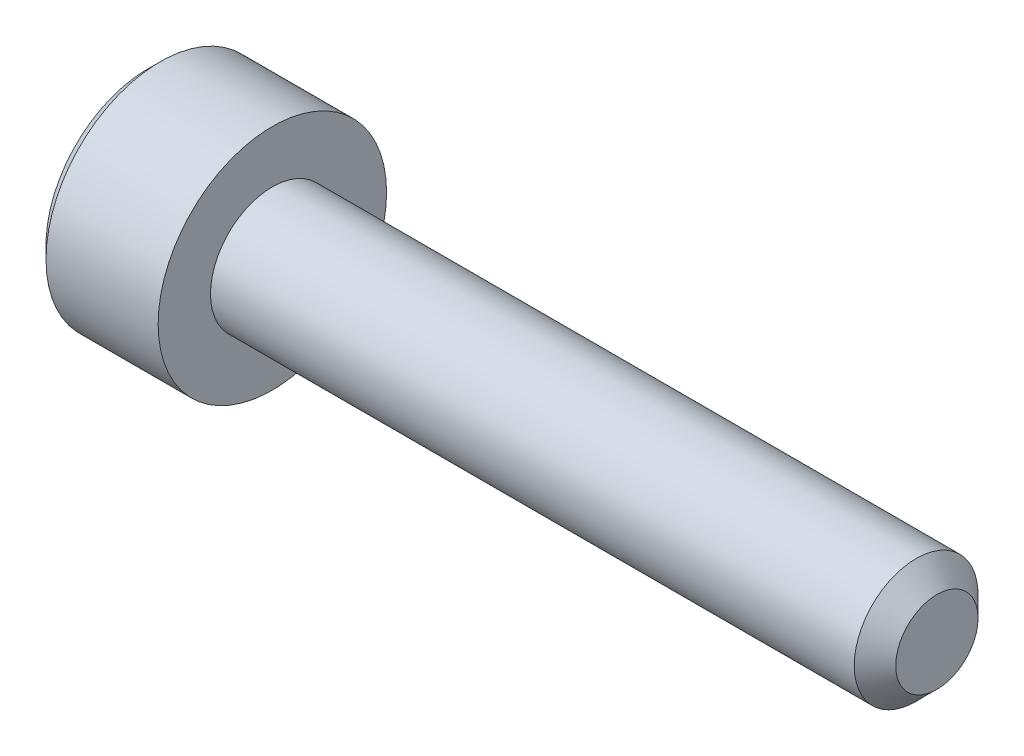
SolidWorks part; units mm, degrees
material "AISI Type 316L stainless steel"
ref_plane "Front Plane" through (0, 0, 0) normal (0, 0, 1) x (1, 0, 0)
ref_plane "Top Plane" through (0, 0, 0) normal (0, 1, 0) x (1, 0, 0)
ref_plane "Right Plane" through (0, 0, 0) normal (1, 0, 0) x (0, 0, -1)
sketch "Sketch1" plane through (0, 0, 0) normal (0, 0, 1) x (1, 0, 0)
  line L0 (-88.7055, 0) -> (96.9812, 0) construction
  line L1 (0, 0) -> (0, 2.75)
  line L2 (0, 2.75) -> (3, 2.75)
  line L4 (19, 0) -> (19, 1.49)
  line L5 (19, 1.49) -> (3, 1.49)
  line L6 (3, 1.49) -> (3, 2.75)
  line L7 (0, 0) -> (19, 0)
  dimension "D1" = 16
  dimension "D2" = 3
  dimension "D3" = 2.75
  dimension "D4" = 1.49
revolve "Revolve1" add sketch "Sketch1" angle 360 about L0
chamfer "Chamfer1" distance 0.5 angle 45 1 edges at (19, 0, 1.49)
chamfer "Chamfer2" distance 0.3 angle 45 1 edges at (0, 0, 2.75)
sketch "Sketch3" plane through (0, 0, 0) normal (1, 0, 0) x (0, 0, -1)
  line L1 (-1.4434, 0) -> (-0.7217, -1.25)
  line L2 (-0.7217, -1.25) -> (0.7217, -1.25)
  line L3 (0.7217, -1.25) -> (1.4434, 0)
  line L4 (1.4434, 0) -> (0.7217, 1.25)
  line L5 (0.7217, 1.25) -> (-0.7217, 1.25)
  line L6 (-0.7217, 1.25) -> (-1.4434, 0)
  circle A0 centre (0, 0) radius 1.25 construction
extrude "Cut-Extrude1" cut sketch "Sketch3" along normal blind 2.5
chamfer "Chamfer3" distance 0.3 angle 45 6 edges at (0, 1.25, 0) (0, 0.625, 1.0825) (0, -0.625, 1.0825) (0, -1.25, 0) (0, -0.625, -1.0825) (0, 0.625, -1.0825)
sketch "Sketch5" plane through (19, 0, 0) normal (1, 0, 0) x (0, 0, -1)
  circle A0 centre (0, 0) radius 1.49
curve "Helix/Spiral1" pitch 0.5 height 20 turns 40
sketch "Sketch8" plane through (0, 0, 0) normal (0, 1, 0) x (1, 0, 0)
  line L0 (19, 1.49) -> (19, 1.1111) construction
  line L1 (19.0625, 1.2194) -> (19.3281, 1.6794)
  line L2 (19.3281, 1.6794) -> (18.6719, 1.6794)
  line L3 (18.6719, 1.6794) -> (18.9375, 1.2194)
  line L4 (19, -0.99) -> (19, 0.99) construction
  circle A0 centre (19, 1.49) radius 0.1894 construction
  arc A1 (19.0625, 1.2194) -> (18.9375, 1.2194) centre (19, 1.2555) cw
  dimension "D2" = 0.0722
  dimension "D1" = 0.3789
sweep "Cut-Sweep1" [suppressed] cut profiles "Sketch8" path "Helix/Spiral1"
equation "\"length\"= 16"
equation "\"D1@Sketch1\"=\"length\""
